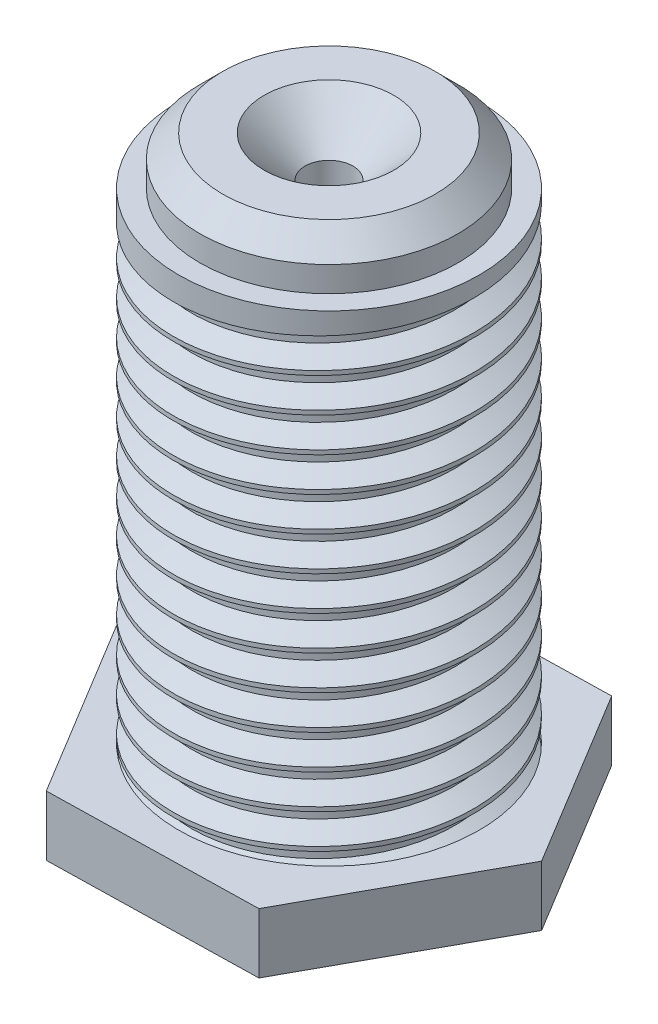
SolidWorks part; units mm, degrees
material "6061-T6 (SS)"
ref_plane "Front Plane" through (0, 0, 0) normal (0, 0, 1) x (1, 0, 0)
ref_plane "Top Plane" through (0, 0, 0) normal (0, 1, 0) x (1, 0, 0)
ref_plane "Right Plane" through (0, 0, 0) normal (1, 0, 0) x (0, 0, -1)
ref_axis "Axis1" through (0, 110.1512, 0) along (0, -1, 0)
sketch "Sketch1" plane through (0, 0, 0) normal (0, 0, 1) x (1, 0, 0)
  line L0 (-15.875, 50.8) -> (-13.6487, 50.8)
  line L1 (-15.875, 0) -> (-15.875, 50.8)
  line L2 (-13.6487, 50.8) -> (-13.6487, 55.88)
  line L3 (-13.6487, 55.88) -> (-6.858, 55.88)
  line L6 (-15.875, 0) -> (0, 0)
  line L8 (0, 110.1512) -> (0, -76.4241) construction
  line L9 (0, 49.022) -> (0, 0)
  line L10 (-6.858, 55.88) -> (0, 49.022)
  dimension "D1" = 15.875
  dimension "D2" = 50.8
  dimension "D3" = 135
  dimension "D4" = 6.858
  dimension "D5" = 13.6487
  dimension "D7" = 5.08
revolve "Revolve1" add sketch "Sketch1" angle 360 about axis through (0, 110.1512, 0) along (0, -1, 0)
cosmetic thread "Cosmetic Thread1" parameters "D2"=27.4295
ref_plane "Plane2" through (0, 110.1512, 0) normal (-1, 0, 0) x (0, 0, 1)
sketch "Sketch12" plane through (0, 0, 0) normal (0, -1, 0) x (1, 0, 0)
  line L1 (-21.992, 0.4698) -> (-11.4029, -18.8107)
  line L2 (-11.4029, -18.8107) -> (10.5891, -19.2806)
  line L3 (10.5891, -19.2806) -> (21.992, -0.4698)
  line L4 (21.992, -0.4698) -> (11.4029, 18.8107)
  line L5 (11.4029, 18.8107) -> (-10.5891, 19.2806)
  line L6 (-10.5891, 19.2806) -> (-21.992, 0.4698)
  circle A0 centre (0, 0) radius 19.05 construction
  dimension "D1" = 38.1
extrude "Boss-Extrude2" add sketch "Sketch12" along normal blind 6.35
ref_plane "Plane4" through (0, 110.1512, 0) normal (-1, 0, 0) x (0, 0, 1)
ref_plane "Plane6" through (0, 110.1512, 0) normal (-1, 0, 0) x (0, 0, 1)
chamfer "Chamfer2" distance 2.413 1 edges at (0, 55.88, 13.6487)
thread "Thread1" pitch 3.6286 method cut profile "Thread Profile1" start angle 0, offset 0, length 0, pitch 3.6286, diameter 31.75
ref_plane "Plane7" through (-15.875, 50.8, 0) normal (0, 0, 1) x (-1, 0, 0)
sketch "Thread Profile1" plane through (-15.875, 50.8, 0) normal (0, 0, 1) x (-1, 0, 0)
  line L0 (0, 0) -> (0, 3.6286) construction
  line L11 (0, 0) -> (0, 3.175)
  line L12 (0, 3.175) -> (-1.964, 2.0411)
  line L13 (-1.964, 2.0411) -> (-1.964, 1.1339)
  line L15 (-1.964, 1.1339) -> (0, 0)
  line L17 (-1.964, 1.5875) -> (0, 1.5875) construction
  point P2 (0, 0)
  dimension "Pitch" = 3.6286
  dimension "Profile_Angle" = 60
  dimension "Profile_Land" = 0.9071
  dimension "Profile_Height" = 1.964
sketch "Sketch13" plane through (0, -6.35, 0) normal (0, -1, 0) x (1, 0, 0)
  circle A0 centre (0, 0) radius 2.54
  dimension "D1" = 5.08
extrude "Cut-Extrude1" cut sketch "Sketch13" against normal through all
